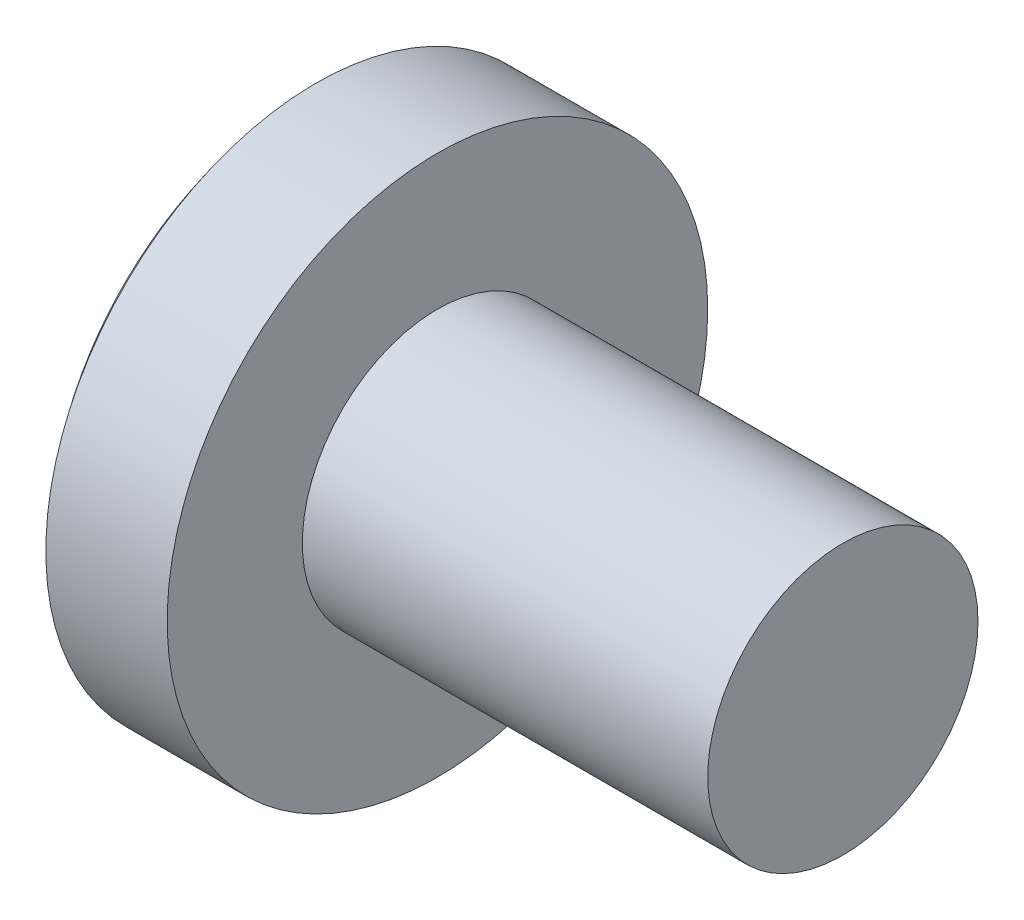
SolidWorks part; units mm, degrees
ref_plane "Front" through (0, 0, 0) normal (0, 0, 1) x (1, 0, 0)
ref_plane "Top" through (0, 0, 0) normal (0, 1, 0) x (1, 0, 0)
ref_plane "Right" through (0, 0, 0) normal (1, 0, 0) x (0, 0, -1)
sketch "Sketch1" plane through (0, 0, 0) normal (0, 0, 1) x (1, 0, 0)
  line L0 (4.6, 1) -> (2.4, 1)
  line L1 (1.6, 1.3) -> (1.6, 2)
  line L2 (1.6, 2) -> (0.702, 2)
  line L3 (2.4, 1) -> (1.9, 1) construction
  line L4 (4.6, 1) -> (4.6, 0)
  line L5 (4.5158, 0) -> (-13.5157, 0) construction
  line L6 (4.6, 0) -> (0, 0)
  line L7 (2.4, 1) -> (1.6, 1)
  line L8 (1.6, 1) -> (1.6, 1.3)
  arc A0 (0.702, 2) -> (0, 0) centre (3.2, 0) ccw
  arc A1 (1.6, 1.3) -> (1.9, 1) centre (1.9, 1.3) ccw construction
  dimension "k" = 1.6
revolve "Base" add sketch "Sketch1" angle 360 about L5
cosmetic thread "ThreadCosmetic1" parameters "bb"=3, "THD_MINOR"=1.567
sketch "Sketch6" plane through (0, 0, 0) normal (1, 0, 0) x (0, 0, -1)
  line L0 (-1.9271, 0) -> (2.0512, 0) construction
  line L1 (0, 1.8651) -> (0, -2.0207) construction
  line L2 (0.19, 0.19) -> (0.19, 0.95)
  line L3 (0.19, 0.95) -> (-0.19, 0.95)
  line L4 (-0.19, 0.19) -> (-0.19, 0.95)
  line L5 (0.19, 0.19) -> (0.95, 0.19)
  line L6 (0.95, 0.19) -> (0.95, -0.19)
  line L7 (-0.95, 0.19) -> (-0.95, -0.19)
  line L8 (-0.19, 0.19) -> (-0.95, 0.19)
  line L9 (-0.19, -0.19) -> (-0.95, -0.19)
  line L10 (0.19, -0.19) -> (0.95, -0.19)
  line L11 (-0.19, -0.19) -> (-0.19, -0.95)
  line L12 (0.19, -0.95) -> (-0.19, -0.95)
  line L13 (0.19, -0.19) -> (0.19, -0.95)
  point P16 (-0.95, 0)
  point P17 (0.95, 0)
extrude "CrossRecess" cut sketch "Sketch6" along normal blind 1.12
fillet "Fillet5" radius 0.3 4 edges at (0.5657, -0.19, 0.19) (0.5657, -0.19, -0.19) (0.5657, 0.19, 0.19) (0.5657, 0.19, -0.19)
draft "Draft1" type of draft neutral plane draft angle 30 neutral plane "Right" faces to draft 4 face at (0.6336, -0.95, 0) face at (0.6336, 0, -0.95) face at (0.6336, 0, 0.95) face at (0.6336, 0.95, 0) neutral plane through (0, 0, 0) neutral plane normal (1, 0, 0) reverse direction yes parameters "D1"=30
sketch "Sketch7" plane through (0, 0, 0) normal (1, 0, 0) x (0, 0, -1)
  line L0 (-2.0126, 0) -> (1.9757, 0) construction
  line L1 (0, 1.9314) -> (0, -2.0126) construction
  line L2 (0, 0) -> (1.5555, 1.5555) construction
  line L3 (0, 0.2839) -> (0.6718, 0.6718)
  line L4 (-1.5402, 1.5402) -> (0, 0) construction
  line L5 (0.2839, 0) -> (0.6718, 0.6718)
  line L6 (0, -0.2839) -> (0.6718, -0.6718)
  line L7 (0.2839, 0) -> (0.6718, -0.6718)
  line L8 (-0.2839, 0) -> (-0.6718, -0.6718)
  line L9 (0, -0.2839) -> (-0.6718, -0.6718)
  line L10 (-0.2839, 0) -> (-0.6718, 0.6718)
  line L11 (0, 0.2839) -> (-0.6718, 0.6718)
  dimension "D3" = 15
extrude "Cut-Extrude3" [suppressed] cut sketch "Sketch7" along normal blind 40.2 draft 9
sketch "Sketch8" plane through (0, 0, 0) normal (0, 0, 1) x (1, 0, 0)
  line L0 (-20.4, 1) -> (-21.4, 0.7835)
  line L1 (-21.4, 0.7835) -> (1.6, 0.7835)
  line L2 (4.6, -1) -> (4.6, 1) construction
  line L3 (1.6, -2) -> (1.6, 2) construction
  line L6 (1.6, 0.7835) -> (1.6, 2)
  line L7 (1.6, 2) -> (-20.4, 2)
  line L8 (-20.4, 2) -> (-20.4, 1)
  line L9 (73.4853, 0) -> (63.9694, 0) construction
  dimension "x" = 1
sketch "Sketch9" plane through (0, 0, 0) normal (0, 0, 1) x (1, 0, 0)
  line L0 (4.6, 0.8125) -> (4.7082, 1)
  line L1 (4.7082, 1) -> (4.7082, 1.2165)
  line L2 (4.7082, 1.2165) -> (4.4917, 1.2165)
  line L3 (4.4917, 1.2165) -> (4.4917, 1)
  line L4 (4.4917, 1) -> (4.6, 0.8125)
  line L5 (4.6, -1) -> (4.6, 1) construction
  line L6 (0, 0) -> (76.7811, 0) construction
  dimension "D1" = 2
  dimension "D2" = 0.2165
revolve "Cut-Revolve10" [suppressed] cut sketch "Sketch9" angle 360 about L6
pattern_linear "LPattern10" [suppressed] count 12 spacing 0.2598 along (-1, 0, 0) of bodies 105
equation "\"D1@Sketch6\" = \"m@Sketch6\" / 5"
equation "\"D1@CrossRecess\" = 0.7*\"k@Sketch1\""
equation "\"D1@Sketch9\" = \"d@Sketch1\" "
equation "\"D2@Sketch9\" =  ( \"d@Sketch1\" - \"THD_MINOR@ThreadCosmetic1\" )  / 2"
equation "\"D3@LPattern10\" =\"D2@Sketch9\" * 1.2"
equation "\"D1@LPattern10\" = \"bb@ThreadCosmetic1\" / \"D3@LPattern10\" "
